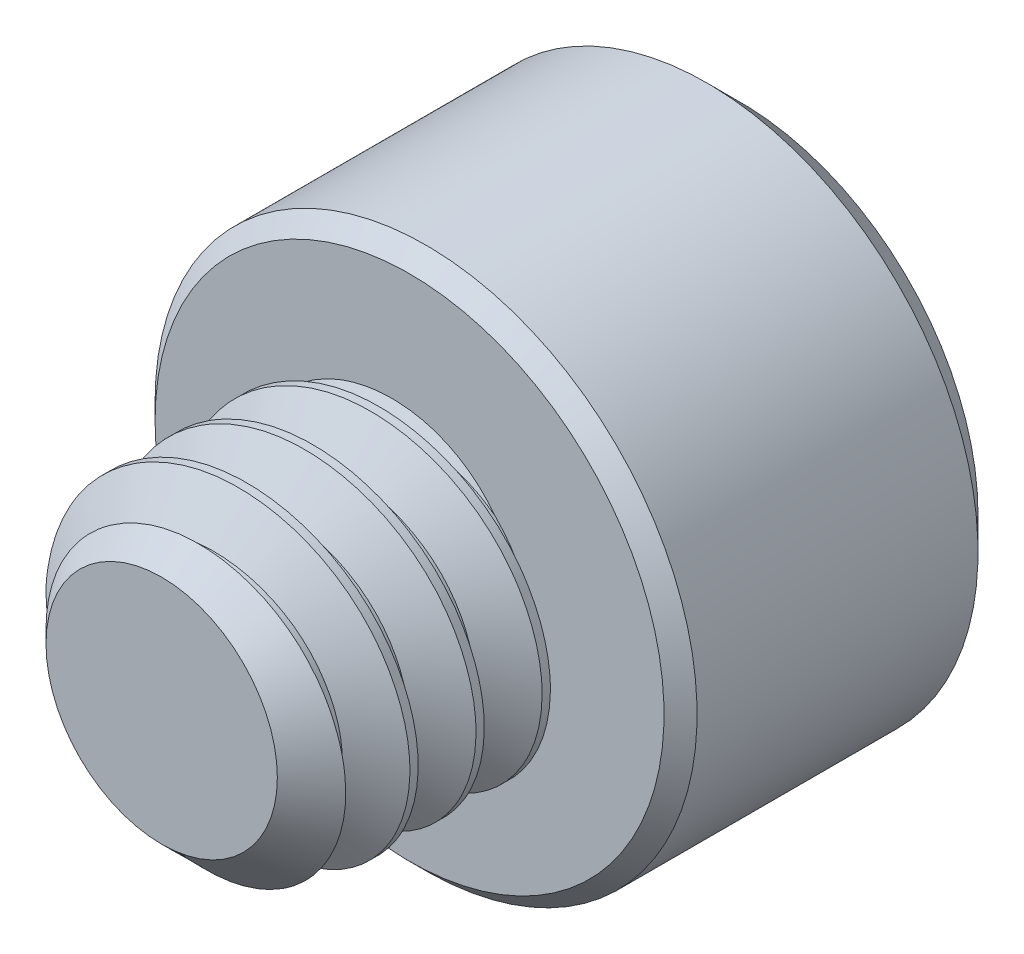
SolidWorks part; units mm, degrees
ref_plane "Front Plane" through (0, 0, 0) normal (0, 0, 1) x (1, 0, 0)
ref_plane "Top Plane" through (0, 0, 0) normal (0, 1, 0) x (1, 0, 0)
ref_plane "Right Plane" through (0, 0, 0) normal (1, 0, 0) x (0, 0, -1)
sketch "Sketch1" plane through (0, 0, 0) normal (0, 0, 1) x (1, 0, 0)
  line L0 (0, 1.5875) -> (0, -1.5875) construction
  circle A0 centre (0, 0) radius 1.5875
  dimension "OD" = 3.175
extrude "Extrude1" add sketch "Sketch1" against normal blind 2.3813
sketch "Sketch2" plane through (0, 0, 0) normal (0, 0, 1) x (1, 0, 0)
  circle A0 centre (0, 0) radius 1.5875 construction
  circle A1 centre (0, 0) radius 1.5875
curve "Helix/Spiral1" pitch 0.635 height 3.0163 radius 1.5875 centre (0, 0, 0) axis (0, 0, -1) start towards (0, 1, 0) parameters "pitch"=0.635
chamfer "Chamfer3" distance 0.4763 angle 45 1 edges at (1.5875, 0, 0)
sketch "Sketch3" plane through (0, 0, 0) normal (1, 0, 0) x (0, 0, -1)
  line L0 (-0.5556, 1.5875) -> (-0.3175, 1.1751)
  line L1 (-0.3175, 1.1751) -> (-0.2381, 1.1751)
  line L2 (-0.2381, 1.1751) -> (0, 1.5875)
  line L3 (-0.5556, 1.5875) -> (0, 1.5875)
  line L4 (-0.2778, 1.5875) -> (-0.2778, 1.1751) construction
  line L5 (-0.4366, 1.3813) -> (-0.1191, 1.3813) construction
  line L6 (0, 1.5875) -> (0, -1.5875) construction
  dimension "D1" = 0.0794
  dimension "D2" = 0.3175
  dimension "D3" = 60
sweep "Cut-Sweep1" cut profiles "Sketch3" path "Helix/Spiral1"
sketch "Sketch6" plane through (0, 0, -2.3813) normal (0, 0, -1) x (-1, 0, 0)
  circle A0 centre (0, 0) radius 2.6035
  dimension "head dia" = 5.207
extrude "Extrude2" add sketch "Sketch6" along normal blind 3.175
sketch "Sketch7" plane through (0, 0, -5.5563) normal (0, 0, -1) x (-1, 0, 0)
  line L1 (0, 1.3748) -> (-1.1906, 0.6874)
  line L2 (-1.1906, 0.6874) -> (-1.1906, -0.6874)
  line L3 (-1.1906, -0.6874) -> (0, -1.3748)
  line L4 (0, -1.3748) -> (1.1906, -0.6874)
  line L5 (1.1906, -0.6874) -> (1.1906, 0.6874)
  line L6 (1.1906, 0.6874) -> (0, 1.3748)
  circle A0 centre (0, 0) radius 1.1906 construction
  dimension "hex dia" = 2.3813
extrude "Cut-Extrude1" cut sketch "Sketch7" against normal blind 1.7859
sketch "Sketch8" plane through (0, 0, -5.5563) normal (0, 0, -1) x (-1, 0, 0)
  circle A0 centre (0, 0) radius 1.3748
extrude "Cut-Extrude2" cut sketch "Sketch8" against normal blind 0.3175 draft 45
chamfer "Chamfer1" distance 0.3175 angle 45 1 edges at (-2.6035, 0, -5.5563)
chamfer "Chamfer2" distance 0.1588 angle 45 1 edges at (-2.6035, 0, -2.3813)
sketch "Sketch9" plane through (0, 0, 0) normal (1, 0, 0) x (0, 0, -1)
  line L0 (0, 1.5875) -> (0, -1.5875) construction
  line L1 (3.4925, 1.5875) -> (3.4925, -1.5875) construction
  line L2 (2.3813, 2.6035) -> (2.3813, -2.6035) construction
  line L3 (5.5563, 2.6035) -> (5.5563, -2.6035) construction
  line L4 (5.5563, 0) -> (0, 0) construction
  dimension "D1" = 3.4925
  dimension "D2" = 3.175
  dimension "D3" = 5.207
  dimension "D4" = 2.3813
equation "\"D3@Helix/Spiral1\" = \"screw length@Extrude1\"+\"pitch@Helix/Spiral1\""
equation "\"D1@Sketch3\" = \"pitch@Helix/Spiral1\"*.125"
equation "\"D2@Sketch3\" = \"pitch@Helix/Spiral1\"*.5"
equation "\"D1@Cut-Extrude1\" = \"hex dia@Sketch7\"*.75"
equation "\"D1@Chamfer1\" = \"head depth@Extrude2\"/10"
equation "\"D1@Sketch9\" = \"pitch@Helix/Spiral1\"*5.5"
equation "\"D1@Chamfer2\" = \"D1@Chamfer1\"/2"
equation "\"D1@Cut-Extrude2\" = \"D1@Chamfer2\"*2"
equation "\"D1@Chamfer3\" = \"pitch@Helix/Spiral1\"*.750"
equation "\"D2@Sketch9\" = \"head depth@Extrude2\""
equation "\"D3@Sketch9\" = \"head dia@Sketch6\""
equation "\"D4@Sketch9\" = \"screw length@Extrude1\""
